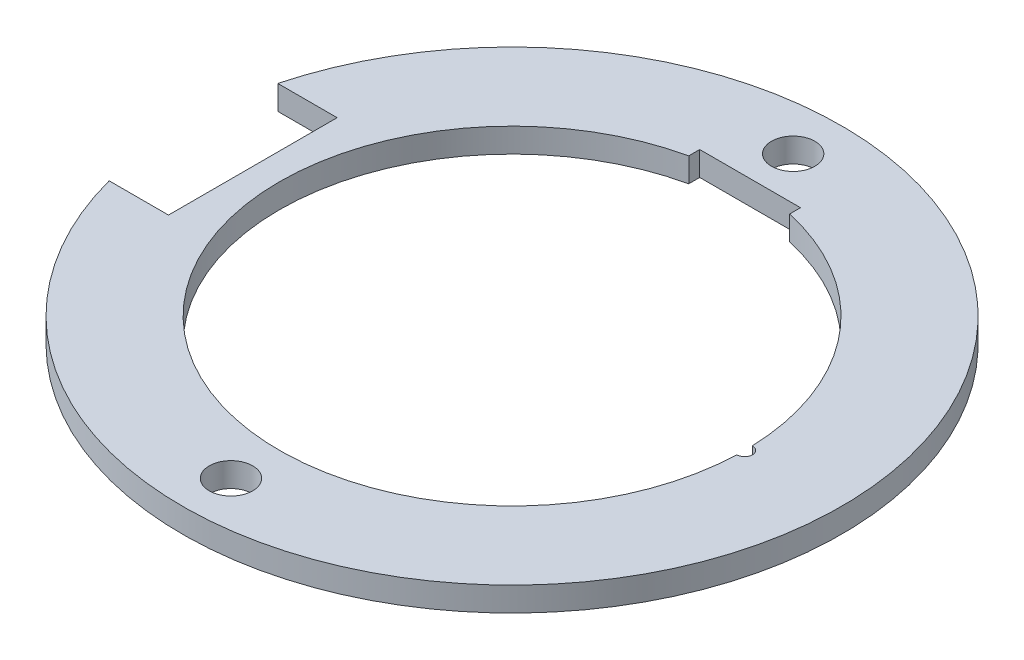
SolidWorks part; units mm, degrees
ref_plane "Front" through (0, 0, 0) normal (0, 0, 1) x (1, 0, 0)
ref_plane "Top" through (0, 0, 0) normal (0, 1, 0) x (1, 0, 0)
ref_plane "Right" through (0, 0, 0) normal (1, 0, 0) x (0, 0, -1)
sketch "Sketch1" plane through (0, 0, 0) normal (0, 1, 0) x (1, 0, 0)
  line L0 (0, -15.24) -> (0, 15.5956) construction
  line L1 (-3.302, 15.5956) -> (3.302, 15.5956)
  line L2 (-3.302, 15.5956) -> (-3.302, 14.878)
  line L3 (3.302, 15.5956) -> (3.302, 14.878)
  circle A0 centre (0, 0) radius 15.24
  circle A1 centre (0, 0) radius 21.59
  dimension "D1" = 30.48
  dimension "D3" = 30.8356
  dimension "D4" = 6.604
  dimension "D2" = 6.35
extrude "Boss-Extrude1" add sketch "Sketch1" along normal mid plane 1.5875 contours A1 A0 L2 L1 L3 region at (-20.9793, 0, 0)
sketch "Sketch2" plane through (0, 0.7937, 0) normal (0, 1, 0) x (1, 0, 0)
  line L0 (0, 18.415) -> (0, -18.415) construction
  line L1 (0, -15.24) -> (0, -21.59) construction
  circle A0 centre (0, 18.415) radius 1.4224
  circle A1 centre (0, -18.415) radius 1.4224
  arc A2 (-3.302, 14.878) -> (3.302, 14.878) centre (0, 0) ccw construction
  circle A3 centre (0, 0) radius 21.59 construction
  dimension "D1" = 2.8448
extrude "Cut-Extrude1" cut sketch "Sketch2" against normal through all
sketch "Sketch3" plane through (0, 0.7937, 0) normal (0, 1, 0) x (1, 0, 0)
  line L0 (-20.8712, 5.5245) -> (-16.9841, 5.5245)
  line L1 (-16.9841, 5.5245) -> (-16.9841, -5.5245)
  line L2 (-16.9841, -5.5245) -> (-20.8712, -5.5245)
  line L3 (-16.9841, -5.5245) -> (-20.8712, -5.5245) construction
  line L4 (-20.8712, 5.5245) -> (-16.9841, 5.5245) construction
  circle A0 centre (0, 0) radius 21.59 construction
  arc A1 (-20.8712, 5.5245) -> (-20.8712, -5.5245) centre (0, 0) ccw
extrude "Cut-Extrude2" cut sketch "Sketch3" against normal through all
sketch "Sketch4" plane through (0, 0.7937, 0) normal (0, 1, 0) x (1, 0, 0)
  line L0 (15.748, 0) -> (-15.24, 0) construction
  circle A0 centre (15.24, 0) radius 0.508
  arc A1 (-3.302, 14.878) -> (3.302, 14.878) centre (0, 0) ccw construction
  dimension "D1" = 30.988
extrude "Cut-Extrude3" cut sketch "Sketch4" against normal through all
